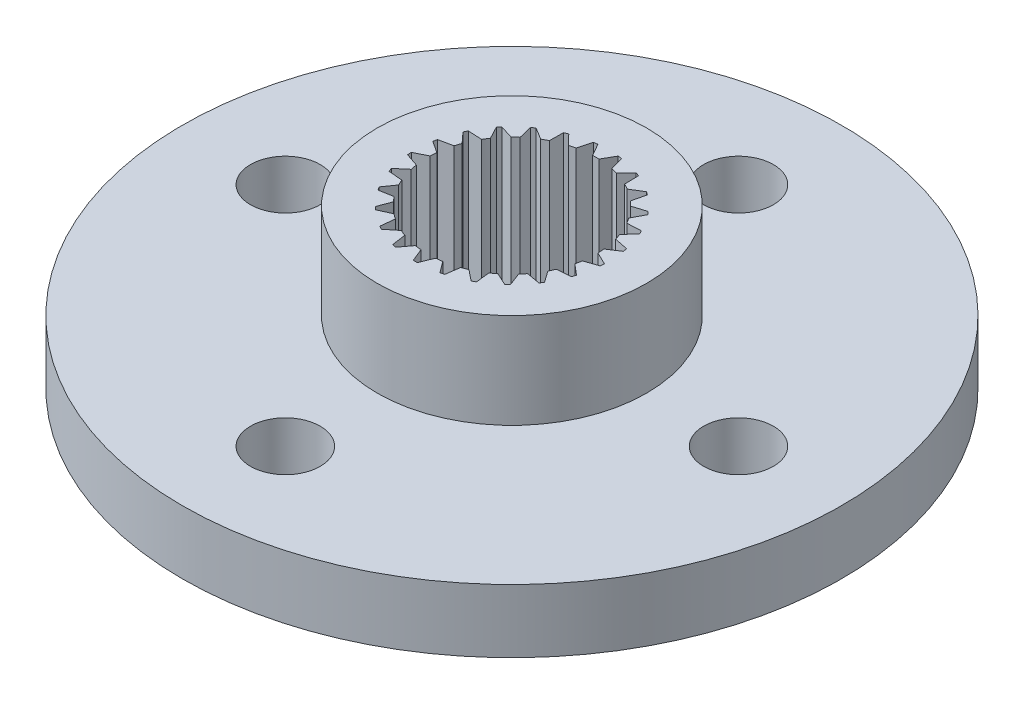
SolidWorks part; units mm, degrees
material "1060 Alloy"
ref_plane "Front Plane" through (0, 0, 0) normal (0, 0, 1) x (1, 0, 0)
ref_plane "Top Plane" through (0, 0, 0) normal (0, 1, 0) x (1, 0, 0)
ref_plane "Right Plane" through (0, 0, 0) normal (1, 0, 0) x (0, 0, -1)
sketch "Sketch2" plane through (0, 0, 0) normal (0, 1, 0) x (1, 0, 0)
  circle A0 centre (0, 0) radius 10.4
  dimension "D1" = 20.8
extrude "Boss-Extrude1" add sketch "Sketch2" along normal blind 2
sketch "Sketch3" plane through (0, 2, 0) normal (0, 1, 0) x (1, 0, 0)
  line L0 (0, 0) -> (0, 12.6294) construction
  line L1 (0, 0) -> (16.4383, 0) construction
  circle A1 centre (0, 7.15) radius 1
  circle A2 centre (7.15, 0) radius 1
  circle A3 centre (0, -7.15) radius 1
  circle A4 centre (-7.15, 0) radius 1
  dimension "D1" = 14.3
  dimension "D3" = 2
  dimension "D2" = 14.3
sketch "Sketch4" plane through (0, 2, 0) normal (0, 1, 0) x (1, 0, 0)
  circle A0 centre (0, 0) radius 4.25
  dimension "D1" = 8.5
extrude "Boss-Extrude2" add sketch "Sketch4" along normal blind 3
sketch "Sketch5" plane through (0, 5, 0) normal (0, 1, 0) x (1, 0, 0)
  circle A0 centre (0, 0) radius 1.5
  dimension "D1" = 3
extrude "Cut-Extrude2" cut sketch "Sketch5" against normal through all
hole_wizard "M2 Clearance Hole1" positions "Sketch7" profile "Sketch8" hole size "M2" standard "ANSI Metric" end condition through all
sketch "Sketch7" plane through (0, 0, 0) normal (0, -1, 0) x (-1, 0, 0)
  point P0 (0, 7.15)
  point P3 (-7.15, 0)
  point P6 (0, -7.15)
  point P9 (7.15, 0)
sketch "Sketch8" plane through (0, 0, -7.15) normal (1, 0, 0) x (0, 0, -1)
  line L0 (0, 0) -> (0, 5)
  line L1 (0, 5) -> (1.1, 5)
  line L2 (1.1, 5) -> (1.1, 0.025)
  line L3 (1.1, 0.025) -> (1.125, 0)
  line L5 (1.125, 0) -> (0, 0)
  line L6 (-1.1, 0.025) -> (-1.125, 0) construction
  line L11 (0, -6.35) -> (0, 107.95) construction
  dimension "Thru Hole Dia." = 2.2
  dimension "Thru Hole Depth" = 5
  dimension "Near C'Sink Dia." = 2.25
  dimension "Near C'Sink Angle" = 90
sketch "Sketch9" plane through (0, 5, 0) normal (0, 1, 0) x (1, 0, 0)
  line L0 (-2.7326, 1.3548) -> (-2.7857, 1.2419)
  line L1 (-2.9837, 0.6327) -> (-3.007, 0.5101)
  line L2 (-3.0473, -0.1292) -> (-3.0394, -0.2537)
  line L3 (-2.9194, -0.883) -> (-2.8808, -1.0016)
  line L4 (-2.6081, -1.5812) -> (-2.5412, -1.6866)
  line L5 (-2.3893, 1.8957) -> (-2.3098, 1.9918)
  line L6 (-2.1329, -2.1802) -> (-2.0419, -2.2656)
  line L7 (-1.5237, -2.6421) -> (-1.4144, -2.7022)
  line L8 (-0.8188, -2.938) -> (-0.6979, -2.9691)
  line L9 (-0.0624, -3.0494) -> (0.0624, -3.0494)
  line L10 (0.6979, -2.9691) -> (0.8188, -2.938)
  line L11 (1.4144, -2.7022) -> (1.5237, -2.6421)
  line L12 (2.0419, -2.2656) -> (2.1329, -2.1802)
  line L13 (2.9194, -0.883) -> (2.8808, -1.0016)
  line L14 (2.5412, -1.6866) -> (2.6081, -1.5812)
  line L15 (3.0473, -0.1292) -> (3.0394, -0.2537)
  line L16 (2.9837, 0.6327) -> (3.007, 0.5101)
  line L17 (2.7326, 1.3548) -> (2.7857, 1.2419)
  line L18 (2.3098, 1.9918) -> (2.3893, 1.8957)
  line L19 (1.7419, 2.5037) -> (1.8428, 2.4303)
  line L20 (1.0645, 2.8582) -> (1.1806, 2.8123)
  line L21 (0.3203, 3.0331) -> (0.4441, 3.0175)
  line L22 (-0.4441, 3.0175) -> (-0.3203, 3.0331)
  line L23 (-1.0645, 2.8582) -> (-1.1806, 2.8123)
  line L24 (-1.8428, 2.4303) -> (-1.7419, 2.5037)
  arc A0 (0.756, 2.5399) -> (1.1875, 2.369) centre (0, 0) ccw
  arc A1 (1.1875, 2.369) -> (0.756, 2.5399) centre (0, 0) ccw
  spline S0 degree 3 poles (3.0473, -0.1292) (2.9155, -0.0646) (2.7829, 0.0003) (2.6492, 0.0658) knots 0 0 0 0 0.000597 0.000597 0.000597 0.000597
  spline S1 degree 3 poles (2.6365, 0.2667) (2.761, 0.3485) (2.8844, 0.4295) (3.007, 0.5101) knots 0 0 0 0 0.000597 0.000597 0.000597 0.000597
  spline S2 degree 3 poles (3.007, 0.5101) (2.8844, 0.4295) (2.761, 0.3485) (2.6365, 0.2667) knots 0 0 0 0 0.000597 0.000597 0.000597 0.000597
  spline S3 degree 3 poles (2.9837, 0.6327) (2.8399, 0.6624) (2.6954, 0.6924) (2.5496, 0.7226) knots 0 0 0 0 0.000597 0.000597 0.000597 0.000597
  spline S4 degree 3 poles (2.4874, 0.914) (2.5876, 1.0242) (2.6869, 1.1333) (2.7857, 1.2419) knots 0 0 0 0 0.000597 0.000597 0.000597 0.000597
  spline S5 degree 3 poles (2.7326, 1.3548) (2.586, 1.3479) (2.4385, 1.3409) (2.2898, 1.3339) knots 0 0 0 0 0.000597 0.000597 0.000597 0.000597
  spline S6 degree 3 poles (2.1819, 1.5039) (2.2516, 1.6355) (2.3207, 1.7659) (2.3893, 1.8957) knots 0 0 0 0 0.000597 0.000597 0.000597 0.000597
  spline S7 degree 3 poles (2.3098, 1.9918) (2.1695, 1.9487) (2.0284, 1.9053) (1.8861, 1.8615) knots 0 0 0 0 0.000597 0.000597 0.000597 0.000597
  spline S8 degree 3 poles (1.7394, 1.9993) (1.7741, 2.1441) (1.8086, 2.2876) (1.8428, 2.4303) knots 0 0 0 0 0.000597 0.000597 0.000597 0.000597
  spline S9 degree 3 poles (1.7419, 2.5037) (1.6167, 2.427) (1.4909, 2.3498) (1.3639, 2.272) knots 0 0 0 0 0.000597 0.000597 0.000597 0.000597
  spline S10 degree 3 poles (1.1875, 2.369) (1.1852, 2.5179) (1.1829, 2.6655) (1.1806, 2.8123) knots 0 0 0 0 0.000597 0.000597 0.000597 0.000597
  spline S11 degree 3 poles (0.756, 2.5399) (0.8597, 2.6468) (0.9624, 2.7528) (1.0645, 2.8582) knots 0 0 0 0 0.000597 0.000597 0.000597 0.000597
  spline S12 degree 3 poles (1.0645, 2.8582) (0.9624, 2.7528) (0.8597, 2.6468) (0.756, 2.5399) knots 0 0 0 0 0.000597 0.000597 0.000597 0.000597
  spline S13 degree 3 poles (0.5611, 2.5899) (0.5218, 2.7336) (0.4828, 2.8759) (0.4441, 3.0175) knots 0 0 0 0 0.000597 0.000597 0.000597 0.000597
  spline S14 degree 3 poles (0.1007, 2.6481) (0.1744, 2.7774) (0.2476, 2.9056) (0.3203, 3.0331) knots 0 0 0 0 0.000597 0.000597 0.000597 0.000597
  spline S15 degree 3 poles (0.3203, 3.0331) (0.2476, 2.9056) (0.1744, 2.7774) (0.1007, 2.6481) knots 0 0 0 0 0.000597 0.000597 0.000597 0.000597
  spline S16 degree 3 poles (-0.1007, 2.6481) (-0.1744, 2.7774) (-0.2476, 2.9056) (-0.3203, 3.0331) knots 0 0 0 0 0.000597 0.000597 0.000597 0.000597
  spline S17 degree 3 poles (-0.5611, 2.5899) (-0.5218, 2.7336) (-0.4828, 2.8759) (-0.4441, 3.0175) knots 0 0 0 0 0.000597 0.000597 0.000597 0.000597
  spline S18 degree 3 poles (-0.4441, 3.0175) (-0.4828, 2.8759) (-0.5218, 2.7336) (-0.5611, 2.5899) knots 0 0 0 0 0.000597 0.000597 0.000597 0.000597
  spline S19 degree 3 poles (-0.756, 2.5399) (-0.8597, 2.6468) (-0.9624, 2.7528) (-1.0645, 2.8582) knots 0 0 0 0 0.000597 0.000597 0.000597 0.000597
  spline S20 degree 3 poles (-1.1875, 2.369) (-1.1852, 2.5179) (-1.1829, 2.6655) (-1.1806, 2.8123) knots 0 0 0 0 0.000597 0.000597 0.000597 0.000597
  spline S21 degree 3 poles (-1.1806, 2.8123) (-1.1829, 2.6655) (-1.1852, 2.5179) (-1.1875, 2.369) knots 0 0 0 0 0.000597 0.000597 0.000597 0.000597
  spline S22 degree 3 poles (-1.3639, 2.272) (-1.4909, 2.3498) (-1.6167, 2.427) (-1.7419, 2.5037) knots 0 0 0 0 0.000597 0.000597 0.000597 0.000597
  spline S23 degree 3 poles (-1.7394, 1.9993) (-1.7741, 2.1441) (-1.8086, 2.2876) (-1.8428, 2.4303) knots 0 0 0 0 0.000597 0.000597 0.000597 0.000597
  spline S24 degree 3 poles (-1.8428, 2.4303) (-1.8086, 2.2876) (-1.7741, 2.1441) (-1.7394, 1.9993) knots 0 0 0 0 0.000597 0.000597 0.000597 0.000597
  spline S25 degree 3 poles (-1.8861, 1.8615) (-2.0284, 1.9053) (-2.1695, 1.9487) (-2.3098, 1.9918) knots 0 0 0 0 0.000597 0.000597 0.000597 0.000597
  spline S26 degree 3 poles (-2.1819, 1.5039) (-2.2516, 1.6355) (-2.3207, 1.7659) (-2.3893, 1.8957) knots 0 0 0 0 0.000597 0.000597 0.000597 0.000597
  spline S27 degree 3 poles (-2.3893, 1.8957) (-2.3207, 1.7659) (-2.2516, 1.6355) (-2.1819, 1.5039) knots 0 0 0 0 0.000597 0.000597 0.000597 0.000597
  spline S28 degree 3 poles (-2.2898, 1.3339) (-2.4385, 1.3409) (-2.586, 1.3479) (-2.7326, 1.3548) knots 0 0 0 0 0.000597 0.000597 0.000597 0.000597
  spline S29 degree 3 poles (-2.4874, 0.914) (-2.5876, 1.0242) (-2.6869, 1.1333) (-2.7857, 1.2419) knots 0 0 0 0 0.000597 0.000597 0.000597 0.000597
  spline S30 degree 3 poles (-2.7857, 1.2419) (-2.6869, 1.1333) (-2.5876, 1.0242) (-2.4874, 0.914) knots 0 0 0 0 0.000597 0.000597 0.000597 0.000597
  spline S31 degree 3 poles (-2.5496, 0.7226) (-2.6954, 0.6924) (-2.8399, 0.6624) (-2.9837, 0.6327) knots 0 0 0 0 0.000597 0.000597 0.000597 0.000597
  spline S32 degree 3 poles (-2.6365, 0.2667) (-2.761, 0.3485) (-2.8844, 0.4295) (-3.007, 0.5101) knots 0 0 0 0 0.000597 0.000597 0.000597 0.000597
  spline S33 degree 3 poles (-3.007, 0.5101) (-2.8844, 0.4295) (-2.761, 0.3485) (-2.6365, 0.2667) knots 0 0 0 0 0.000597 0.000597 0.000597 0.000597
  spline S34 degree 3 poles (-2.6492, 0.0658) (-2.7829, 0.0003) (-2.9155, -0.0646) (-3.0473, -0.1292) knots 0 0 0 0 0.000597 0.000597 0.000597 0.000597
  spline S35 degree 3 poles (-2.62, -0.3973) (-2.7609, -0.3491) (-2.9006, -0.3013) (-3.0394, -0.2537) knots 0 0 0 0 0.000597 0.000597 0.000597 0.000597
  spline S36 degree 3 poles (-3.0394, -0.2537) (-2.9006, -0.3013) (-2.7609, -0.3491) (-2.62, -0.3973) knots 0 0 0 0 0.000597 0.000597 0.000597 0.000597
  spline S37 degree 3 poles (-2.5823, -0.5951) (-2.6956, -0.6918) (-2.8078, -0.7876) (-2.9194, -0.883) knots 0 0 0 0 0.000597 0.000597 0.000597 0.000597
  spline S38 degree 3 poles (-2.4389, -1.0364) (-2.5874, -1.0247) (-2.7345, -1.0132) (-2.8808, -1.0016) knots 0 0 0 0 0.000597 0.000597 0.000597 0.000597
  spline S39 degree 3 poles (-2.8808, -1.0016) (-2.7345, -1.0132) (-2.5874, -1.0247) (-2.4389, -1.0364) knots 0 0 0 0 0.000597 0.000597 0.000597 0.000597
  spline S40 degree 3 poles (-2.3532, -1.2186) (-2.4388, -1.3404) (-2.5237, -1.4612) (-2.6081, -1.5812) knots 0 0 0 0 0.000597 0.000597 0.000597 0.000597
  spline S41 degree 3 poles (-2.6081, -1.5812) (-2.5237, -1.4612) (-2.4388, -1.3404) (-2.3532, -1.2186) knots 0 0 0 0 0.000597 0.000597 0.000597 0.000597
  spline S42 degree 3 poles (-2.1045, -1.6104) (-2.2512, -1.636) (-2.3966, -1.6614) (-2.5412, -1.6866) knots 0 0 0 0 0.000597 0.000597 0.000597 0.000597
  spline S43 degree 3 poles (-2.5412, -1.6866) (-2.3966, -1.6614) (-2.2512, -1.636) (-2.1045, -1.6104) knots 0 0 0 0 0.000597 0.000597 0.000597 0.000597
  spline S44 degree 3 poles (-1.9762, -1.7655) (-2.0289, -1.9048) (-2.081, -2.0429) (-2.1329, -2.1802) knots 0 0 0 0 0.000597 0.000597 0.000597 0.000597
  spline S45 degree 3 poles (-2.1329, -2.1802) (-2.081, -2.0429) (-2.0289, -1.9048) (-1.9762, -1.7655) knots 0 0 0 0 0.000597 0.000597 0.000597 0.000597
  spline S46 degree 3 poles (-1.6379, -2.0832) (-1.7737, -2.1445) (-1.9082, -2.2052) (-2.0419, -2.2656) knots 0 0 0 0 0.000597 0.000597 0.000597 0.000597
  spline S47 degree 3 poles (-2.0419, -2.2656) (-1.9082, -2.2052) (-1.7737, -2.1445) (-1.6379, -2.0832) knots 0 0 0 0 0.000597 0.000597 0.000597 0.000597
  spline S48 degree 3 poles (-1.4751, -2.2015) (-1.4914, -2.3495) (-1.5076, -2.4962) (-1.5237, -2.6421) knots 0 0 0 0 0.000597 0.000597 0.000597 0.000597
  spline S49 degree 3 poles (-1.5237, -2.6421) (-1.5076, -2.4962) (-1.4914, -2.3495) (-1.4751, -2.2015) knots 0 0 0 0 0.000597 0.000597 0.000597 0.000597
  spline S50 degree 3 poles (-1.0684, -2.4251) (-1.1846, -2.5182) (-1.2998, -2.6105) (-1.4144, -2.7022) knots 0 0 0 0 0.000597 0.000597 0.000597 0.000597
  spline S51 degree 3 poles (-1.4144, -2.7022) (-1.2998, -2.6105) (-1.1846, -2.5182) (-1.0684, -2.4251) knots 0 0 0 0 0.000597 0.000597 0.000597 0.000597
  spline S52 degree 3 poles (-0.8812, -2.4992) (-0.8603, -2.6466) (-0.8395, -2.7927) (-0.8188, -2.938) knots 0 0 0 0 0.000597 0.000597 0.000597 0.000597
  spline S53 degree 3 poles (-0.8188, -2.938) (-0.8395, -2.7927) (-0.8603, -2.6466) (-0.8812, -2.4992) knots 0 0 0 0 0.000597 0.000597 0.000597 0.000597
  spline S54 degree 3 poles (-0.6979, -2.9691) (-0.6098, -2.8517) (-0.5212, -2.7337) (-0.4318, -2.6146) knots 0 0 0 0 0.000597 0.000597 0.000597 0.000597
  spline S55 degree 3 poles (-0.232, -2.6398) (-0.175, -2.7774) (-0.1186, -2.9138) (-0.0624, -3.0494) knots 0 0 0 0 0.000597 0.000597 0.000597 0.000597
  spline S56 degree 3 poles (-0.0624, -3.0494) (-0.1186, -2.9138) (-0.175, -2.7774) (-0.232, -2.6398) knots 0 0 0 0 0.000597 0.000597 0.000597 0.000597
  spline S57 degree 3 poles (0.0624, -3.0494) (0.1186, -2.9138) (0.175, -2.7774) (0.232, -2.6398) knots 0 0 0 0 0.000597 0.000597 0.000597 0.000597
  spline S58 degree 3 poles (0.4318, -2.6146) (0.5212, -2.7337) (0.6098, -2.8517) (0.6979, -2.9691) knots 0 0 0 0 0.000597 0.000597 0.000597 0.000597
  spline S59 degree 3 poles (0.6979, -2.9691) (0.6098, -2.8517) (0.5212, -2.7337) (0.4318, -2.6146) knots 0 0 0 0 0.000597 0.000597 0.000597 0.000597
  spline S60 degree 3 poles (0.8188, -2.938) (0.8395, -2.7927) (0.8603, -2.6466) (0.8812, -2.4992) knots 0 0 0 0 0.000597 0.000597 0.000597 0.000597
  spline S61 degree 3 poles (1.0684, -2.4251) (1.1846, -2.5182) (1.2998, -2.6105) (1.4144, -2.7022) knots 0 0 0 0 0.000597 0.000597 0.000597 0.000597
  spline S62 degree 3 poles (1.4144, -2.7022) (1.2998, -2.6105) (1.1846, -2.5182) (1.0684, -2.4251) knots 0 0 0 0 0.000597 0.000597 0.000597 0.000597
  spline S63 degree 3 poles (1.5237, -2.6421) (1.5076, -2.4962) (1.4914, -2.3495) (1.4751, -2.2015) knots 0 0 0 0 0.000597 0.000597 0.000597 0.000597
  spline S64 degree 3 poles (1.6379, -2.0832) (1.7737, -2.1445) (1.9082, -2.2052) (2.0419, -2.2656) knots 0 0 0 0 0.000597 0.000597 0.000597 0.000597
  spline S65 degree 3 poles (2.0419, -2.2656) (1.9082, -2.2052) (1.7737, -2.1445) (1.6379, -2.0832) knots 0 0 0 0 0.000597 0.000597 0.000597 0.000597
  spline S66 degree 3 poles (2.1329, -2.1802) (2.081, -2.0429) (2.0289, -1.9048) (1.9762, -1.7655) knots 0 0 0 0 0.000597 0.000597 0.000597 0.000597
  spline S67 degree 3 poles (2.1045, -1.6104) (2.2512, -1.636) (2.3966, -1.6614) (2.5412, -1.6866) knots 0 0 0 0 0.000597 0.000597 0.000597 0.000597
  spline S68 degree 3 poles (2.5412, -1.6866) (2.3966, -1.6614) (2.2512, -1.636) (2.1045, -1.6104) knots 0 0 0 0 0.000597 0.000597 0.000597 0.000597
  spline S69 degree 3 poles (2.6081, -1.5812) (2.5237, -1.4612) (2.4388, -1.3404) (2.3532, -1.2186) knots 0 0 0 0 0.000597 0.000597 0.000597 0.000597
  spline S70 degree 3 poles (2.4389, -1.0364) (2.5874, -1.0247) (2.7345, -1.0132) (2.8808, -1.0016) knots 0 0 0 0 0.000597 0.000597 0.000597 0.000597
  spline S71 degree 3 poles (2.8808, -1.0016) (2.7345, -1.0132) (2.5874, -1.0247) (2.4389, -1.0364) knots 0 0 0 0 0.000597 0.000597 0.000597 0.000597
  spline S72 degree 3 poles (2.9194, -0.883) (2.8078, -0.7876) (2.6956, -0.6918) (2.5823, -0.5951) knots 0 0 0 0 0.000597 0.000597 0.000597 0.000597
  spline S73 degree 3 poles (2.62, -0.3973) (2.7609, -0.3491) (2.9006, -0.3013) (3.0394, -0.2537) knots 0 0 0 0 0.000597 0.000597 0.000597 0.000597
  spline S74 degree 3 poles (3.0394, -0.2537) (2.9006, -0.3013) (2.7609, -0.3491) (2.62, -0.3973) knots 0 0 0 0 0.000597 0.000597 0.000597 0.000597
extrude "Cut-Extrude3" cut sketch "Sketch9" against normal blind 10 contours A0 A1 | S23 A0 S22 L24 | S26 A0 S25 L5 | S29 A0 S28 L0 | S32 A0 S31 L1 | S35 A0 S34 L2 | S38 A0 S37 L3 | S42 A0 S40 L4 | S46 A0 S44 L6 | S50 A0 S48 L7 | L8 S54 A0 S52 | L9 S57 A0 S55 | L10 S60 A0 S58 | L11 S63 A0 S61 | L12 S66 A0 S64 | L14 S69 A0 S67 | L13 S72 A0 S70 | A0 S73 L15 S0 | L16 S3 A0 S1 | L17 S5 A0 S4 | L18 S7 A0 S6 | L19 S9 A0 S8 | S11 A1 S10 L20 | S14 A0 S13 L21 | S17 A0 S16 L22 | S20 A0 S19 L23 region at (-2.5422, 5, -1.1963) region at (0, 5, 0) region at (-2.1648, 5, -1.7909) region at (-2.7598, 5, -0.5265) region at (-1.6514, 5, -2.273) region at (-2.8041, 5, 0.1764) region at (-1.0343, 5, -2.6123) region at (-2.6721, 5, 0.8682) region at (-0.3521, 5, -2.7874) region at (-2.3722, 5, 1.5055) region at (0.3521, 5, -2.7874) region at (-1.9233, 5, 2.0481) region at (1.0343, 5, -2.6123) region at (-1.3535, 5, 2.4621) region at (1.6514, 5, -2.273) region at (-0.6987, 5, 2.7213) region at (2.1648, 5, -1.7909) region at (0, 5, 2.8096) region at (2.5422, 5, -1.1963) region at (0.6987, 5, 2.7213) region at (2.7598, 5, -0.5265) region at (1.3535, 5, 2.4621) region at (2.8041, 5, 0.1764) region at (1.9233, 5, 2.0481) region at (2.6721, 5, 0.8682) region at (2.3722, 5, 1.5055)
